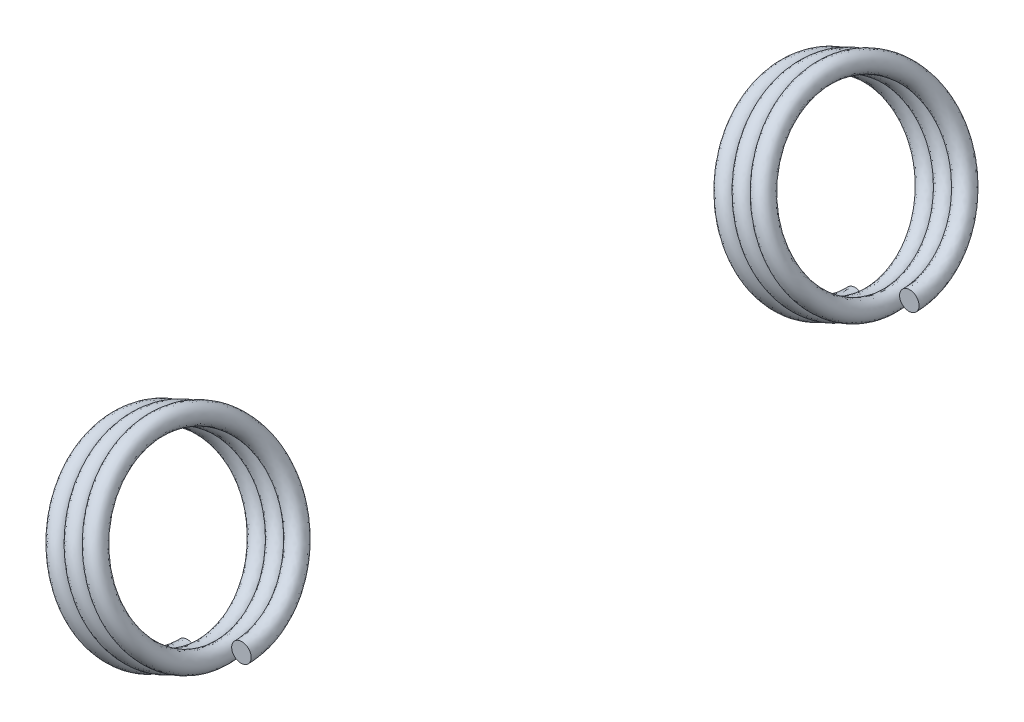
SolidWorks part; units mm, degrees
material "Acero aleado"
ref_plane "Alzado" through (0, 0, 0) normal (0, 0, 1) x (1, 0, 0)
ref_plane "Planta" through (0, 0, 0) normal (0, 1, 0) x (1, 0, 0)
ref_plane "Vista lateral" through (0, 0, 0) normal (1, 0, 0) x (0, 0, -1)
sketch3d "Sk_Plano_muelle_izq"
  point P0 (434.1303, 385.1286, 0)
  point P1 (434.1303, 385.1286, 10)
  point P2 (429.9206, 394.1993, 0)
ref_plane "Plano_muelle_izq" through (504.2575, 234.023, 0) normal (-0.9071, -0.421, 0) x (0, 0, 1)
sketch "Sk_muelle_izq" plane through (504.2575, 234.023, 0) normal (-0.9071, -0.421, 0) x (0, 0, 1)
  circle A0 centre (-26, 166.5855) radius 7.5
  dimension "DIAM1" = 15
curve "Helice_izq" pitch 1.7 height 5.1 turns 3
sweep "Muelle_izq" add path "Helice_izq" circular profile diameter 1.6 parameters "D3"=1.6
sketch3d "Sk_Plano_muelle_dcho"
  point P0 (434.1303, 385.1286, 0)
  point P1 (434.1303, 385.1286, 10)
  point P2 (429.9206, 394.1993, 0)
ref_plane "Plano_muelle_dcho" through (504.2575, 234.023, 0) normal (-0.9071, -0.421, 0) x (0, 0, 1)
sketch "Sk_muelle_dcho" plane through (504.2575, 234.023, 0) normal (-0.9071, -0.421, 0) x (0, 0, 1)
  circle A0 centre (26, 166.5855) radius 7.5
  dimension "DIAM2" = 15
curve "Helice_dcho" pitch 1.7 height 5.1 turns 3
sweep "Muelle_dcho" add path "Helice_dcho" circular profile diameter 1.6 parameters "D3"=1.6
